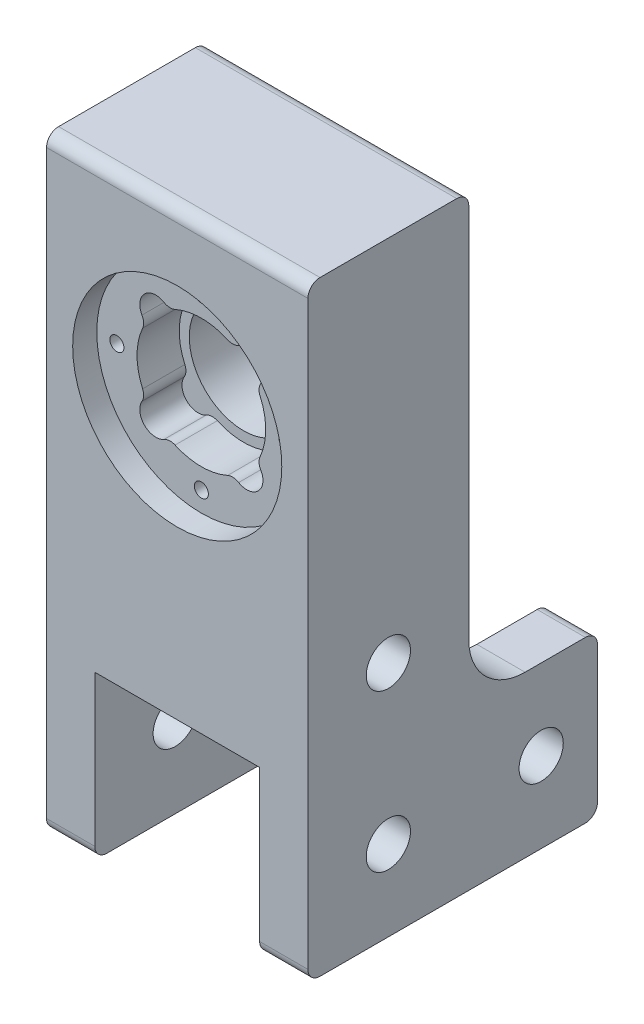
SolidWorks part; units mm, degrees
ref_plane "Front plane" through (0, 0, 0) normal (0, 0, 1) x (1, 0, 0)
ref_plane "Top plane" through (0, 0, 0) normal (0, 1, 0) x (1, 0, 0)
ref_plane "Right plane" through (0, 0, 0) normal (1, 0, 0) x (0, 0, -1)
ref_axis "Axis X" through (0, 0, 0) along (1, 0, 0)
ref_axis "Axis Y" through (0, 0, 0) along (0, 1, 0)
ref_axis "Axis Z" through (0, 0, 0) along (0, 0, 1)
sketch "Sketch1" plane through (0, 0, 0) normal (1, 0, 0) x (0, 0, -1)
  line L1 (10, 65.25) -> (-10, 65.25)
  line L2 (10, 65.25) -> (10, 10.25)
  line L3 (10, 10.25) -> (-10, 10.25)
  line L4 (-10, 65.25) -> (-10, 10.25)
  line L5 (10, 65.25) -> (-10, 10.25) construction
  line L6 (10, 10.25) -> (-10, 65.25) construction
  point P0 (0, 37.75)
  dimension "D1" = 10.25
  dimension "D2" = 20
  dimension "D3" = 55
extrude "Extrude1" add sketch "Sketch1" along normal blind 10.25 and the other way blind 10.25
sketch "Sketch2" plane through (10.25, 0, 0) normal (1, 0, 0) x (0, 0, -1)
  line L0 (10, 10.25) -> (10, 65.25) construction
  line L1 (26, 10) -> (17, 10)
  line L2 (26, 10) -> (26, -10)
  line L3 (26, -10) -> (-26, -10)
  line L4 (-26, 10) -> (-26, -10)
  line L5 (26, 10) -> (-26, -10) construction
  line L6 (26, -10) -> (-26, 10) construction
  line L7 (-10, 65.25) -> (10, 65.25)
  line L8 (-10, 65.25) -> (-10, 17)
  line L9 (-10, 10) -> (10, 10) construction
  line L10 (10, 65.25) -> (10, 17)
  line L11 (-17, 10) -> (-26, 10)
  line L12 (10, 10) -> (-10, 10) construction
  arc A0 (17, 10) -> (10, 17) centre (17, 17) cw
  arc A1 (-17, 10) -> (-10, 17) centre (-17, 17) ccw
  point P0 (0, 0)
  dimension "D3" = 7
  dimension "D1" = 20
  dimension "D2" = 52
extrude "Extrude2" add sketch "Sketch2" along normal blind 6
mirror "Mirror2" about plane through (0, 0, 0) normal (1, 0, 0) of "Extrude2"
sketch "Sketch4" plane through (16.25, 0, 0) normal (1, 0, 0) x (0, 0, -1)
  line L0 (0, 2.75) -> (0, -2.75) construction
  circle A0 centre (0, 0) radius 2.75
  circle A1 centre (19, 0) radius 2.75
  circle A2 centre (-19, 0) radius 2.75
  circle A3 centre (0, 19.5) radius 2.75
  circle A4 centre (0, 51.75) radius 2.75 construction
  dimension "D1" = 5.5
  dimension "D2" = 5.5
  dimension "D4" = 5.5
  dimension "D5" = 5.5
  dimension "D3" = 19
  dimension "D6" = 32.25
  dimension "D7" = 19.5
extrude "Extrude3" cut sketch "Sketch4" against normal through all
sketch "Sketch5" plane through (0, 0, 10) normal (0, 0, 1) x (1, 0, 0)
  line L0 (-16.25, 19.5) -> (16.25, 19.5) construction
  line L1 (-16.25, 65.25) -> (-16.25, 17) construction
  line L2 (16.25, 65.25) -> (16.25, 17) construction
  line L3 (-16.25, 22.25) -> (16.25, 22.25) construction
  line L4 (-16.25, 16.75) -> (16.25, 16.75) construction
  line L5 (-16.25, 54.5) -> (16.25, 54.5) construction
  line L6 (-16.25, 51.75) -> (16.25, 51.75) construction
  line L7 (-16.25, 49) -> (16.25, 49) construction
  line L8 (-6.755, 44) -> (6.755, 44) construction
  line L9 (-10.25, 10) -> (10.25, 10) construction
  line L10 (-10.25, 10) -> (-10.25, -10) construction
  line L11 (10.25, 10) -> (10.25, -10) construction
  circle A0 centre (0, 44) radius 6.755
  dimension "D1" = 5.5
  dimension "D2" = 5.5
  dimension "D5" = 13.51
  dimension "D3" = 19.5
  dimension "D4" = 32.25
  dimension "D7" = 10
  dimension "D8" = 34
extrude "Extrude4" cut sketch "Sketch5" against normal through all
fillet "Fillet2" radius 1.5 10 edges at (13.25, -10, 26) (13.25, 10, 26) (-13.25, 10, 26) (-13.25, -10, 26) (-13.25, -10, -26) (13.25, -10, -26) (13.25, 10, -26) (-13.25, 10, -26) (0, 65.25, 10) (0, 65.25, -10)
sketch "Эскиз1" plane through (0, 0, 10) normal (0, 0, -1) x (-1, 0, 0)
  line L0 (-16.25, 17) -> (-16.25, 63.75) construction
  line L1 (16.25, -10) -> (-16.25, -10)
  line L2 (16.25, -10) -> (16.25, 63.75)
  line L3 (16.25, 63.75) -> (-16.25, 63.75)
  line L4 (-16.25, -10) -> (-16.25, 63.75)
  line L5 (16.25, -10) -> (-16.25, 63.75) construction
  line L6 (16.25, 63.75) -> (-16.25, -10) construction
  line L7 (16.25, 17) -> (16.25, 63.75) construction
  line L8 (16.25, 63.75) -> (-16.25, 63.75) construction
  line L9 (-10.25, -10) -> (-16.25, -10) construction
  point P0 (0, 26.875)
extrude "Вырез-Вытянуть1" cut sketch "Эскиз1" against normal through all
sketch "Эскиз2" plane through (0, 0, 10) normal (0, 0, 1) x (1, 0, 0)
  circle A0 centre (0, 44) radius 13
  dimension "D1" = 26
extrude "Вырез-Вытянуть2" cut sketch "Эскиз2" against normal blind 3
sketch "Эскиз3" plane through (0, 0, 7) normal (0, 0, 1) x (1, 0, 0)
  circle A0 centre (0, 44) radius 8
  circle A1 centre (0, 44) radius 6.755 construction
  arc A2 (-1.9843, 51.75) -> (1.9843, 51.75) centre (0, 52) cw construction
  arc A3 (4.077, 50.8832) -> (6.8832, 48.077) centre (5.6569, 49.6569) cw
  arc A4 (7.75, 45.9843) -> (7.75, 42.0157) centre (8, 44) cw construction
  arc A5 (6.8832, 39.923) -> (4.077, 37.1168) centre (5.6569, 38.3431) cw
  arc A6 (1.9843, 36.25) -> (-1.9843, 36.25) centre (0, 36) cw construction
  arc A7 (-4.077, 37.1168) -> (-6.8832, 39.923) centre (-5.6569, 38.3431) cw
  arc A8 (-7.75, 42.0157) -> (-7.75, 45.9843) centre (-8, 44) cw construction
  arc A9 (-6.8832, 48.077) -> (-4.077, 50.8832) centre (-5.6569, 49.6569) cw
  point P8 (0, 0)
  point P9 (0, 0)
  circle M3 centre (0, 44) radius 6.755
  dimension "D1" = 16
  dimension "D2" = 2
  dimension "D3" = 8
extrude "Вырез-Вытянуть3" cut sketch "Эскиз3" against normal blind 5.25 contours A0 M3 | M3 | A9 A0 | A3 A0 | A5 A0 | A7 A0 region at (7.4975, 41.9462, 7) region at (6.2241, 50.2241, 7) region at (6.2241, 37.7759, 7) region at (-6.2241, 50.2241, 7) region at (-6.2241, 37.7759, 7) region at (0, 44, 7)
fillet "Скругление1" radius 1.5 8 edges at (6.8832, 48.077, 4.375) (6.8832, 39.923, 4.375) (4.077, 37.1168, 4.375) (-4.077, 37.1168, 4.375) (-6.8832, 39.923, 4.375) (-6.8832, 48.077, 4.375) (4.077, 50.8832, 4.375) (-4.077, 50.8832, 4.375)
sketch "Эскиз4" plane through (0, 0, 7) normal (0, 0, 1) x (1, 0, 0)
  circle A0 centre (0, 44) radius 10.5 construction
  circle A1 centre (0, 54.5) radius 0.875
  circle A2 centre (10.5, 44) radius 0.875
  circle A3 centre (0, 33.5) radius 0.875
  circle A4 centre (-10.5, 44) radius 0.875
  point P5 (0, 0)
  point P7 (0, 0)
  dimension "D1" = 21
  dimension "D2" = 1.75
  dimension "D3" = 4
extrude "Вырез-Вытянуть4" cut sketch "Эскиз4" against normal blind 8
fillet "Скругление2" radius 1.5 2 edges at (13.25, -10, 10) (-13.25, -10, 10)
equation "\"print_offset\"= 0.5"
equation "\"prof_width\"= 20'Aluminium profile parameters"
equation "\"D1@Sketch1\"=(\"prof_width\"+\"print_offset\")/2"
equation "\"D3@Sketch1\" = 55.00"
equation "\"D1@Extrude1\"=(\"prof_width\"+\"print_offset\")/2"
equation "\"D2@Extrude1\"=(\"prof_width\"+\"print_offset\")/2"
equation "\"D1@Sketch2\"=\"prof_width\""
equation "\"D1@Sketch4\"=\"print_offset\"+5"
equation "\"D2@Sketch4\"=\"D1@Sketch4\""
equation "\"D4@Sketch4\"=\"D1@Sketch4\""
equation "\"D5@Sketch4\"=\"D1@Sketch4\""
equation "\"D2@Sketch5\"=\"D1@Sketch5\""
equation "\"D1@Sketch5\" = \"print_offset\" + 5.00"
equation "\"D7@Sketch5\"=\"prof_width\"/2"
equation "\"radial_bearing_d1\"= 7.7"
equation "\"radial_bearing_d2\"= 16"
equation "\"radial_bearing_h\"= 5"
equation "\"shaft_d\"= 6"
equation "\"shaft_h\" = 60"
equation "\"central_hole_d\"= 20"
equation "\"sitting_screws_d\"= 34"
equation "\"screw_d\"= 2"
equation "\"screw_hh_d\"= 3.4"
equation "\"screw_h\"= 8"
equation "\"screw_hh_h\"= 2"
equation "\"motor_screw_d\"= 3"
equation "\"motor_screw_hh_d\"= 5.6"
equation "\"motor_screw_h\" = 20"
equation "\"motor_screw_hh_h\"= 2"
equation "\"motor_nut_d\"= 5.4"
equation "\"motor_nut_h\"= 2.8"
equation "\"D5@Sketch5\"=\"radial_bearing_d2\"-(\"radial_bearing_d2\"-\"radial_bearing_d1\")*0.3"
equation "\"D1@Эскиз2\"=\"radial_bearing_d2\"+10"
equation "\"D1@Эскиз3\"=\"radial_bearing_d2\""
equation "\"D1@Вырез-Вытянуть3\"=\"radial_bearing_h\"+\"print_offset\"/2"
equation "\"D1@Эскиз4\"=\"radial_bearing_d2\"+5"
equation "\"D2@Эскиз4\"=\"screw_d\"-\"print_offset\"/2"
equation "\"D1@Вырез-Вытянуть4\"=\"screw_h\""
